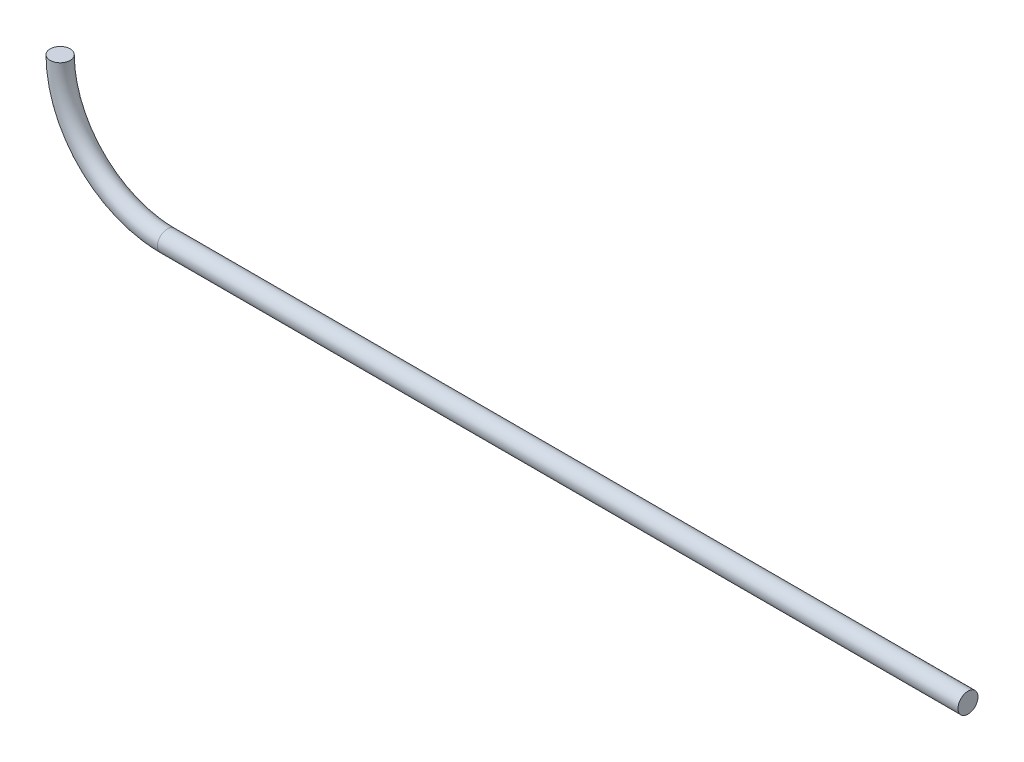
SolidWorks part; units mm, degrees
ref_plane "prox_pulley" through (0, 0, 0) normal (0, 0, 1) x (1, 0, 0)
ref_plane "Top Plane" through (0, 0, 0) normal (0, 1, 0) x (1, 0, 0)
ref_plane "Right Plane" through (0, 0, 0) normal (1, 0, 0) x (0, 0, -1)
sketch "Sketch1" plane through (0, 0, 0) normal (0, 0, 1) x (1, 0, 0)
  line L0 (0, -5.36) -> (40, -5.36)
  circle A0 centre (0, 0) radius 5.36 construction
  arc A1 (-5.36, 0) -> (0, -5.36) centre (0, 0) ccw
  dimension "D1" = 10.72
  dimension "D2" = 40
ref_plane "trans_pulley" through (0, -12, 0) normal (0, 1, 0) x (1, 0, 0)
ref_plane "lower_pulley_center" through (0, -43.67, 0) normal (0, 1, 0) x (1, 0, 0)
ref_axis "pulley_tangent" through (40, -25.194, 0) along (0, 1, 0)
ref_point "tendon_start"
sketch "Sketch6" plane through (0, 0, 0) normal (0, 1, 0) x (1, 0, 0)
  circle A0 centre (-5.36, 0) radius 0.5
  dimension "D1" = 1
sweep "Sweep1" add profiles "Sketch6" path "Sketch1"
